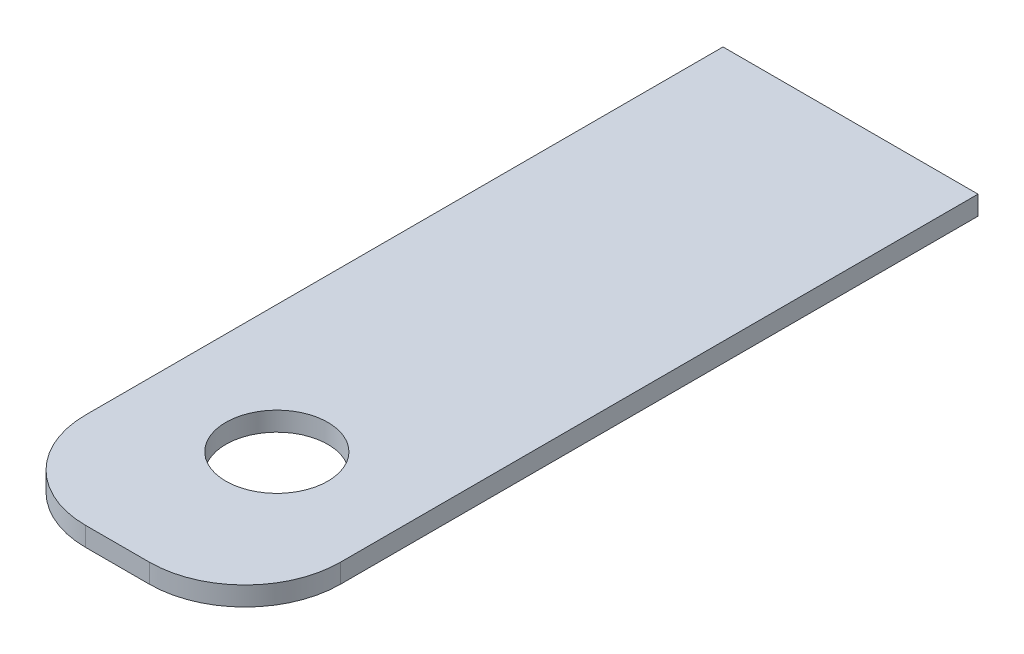
SolidWorks part; units mm, degrees
material "6061-T6 (SS)"
ref_plane "Front Plane" through (0, 0, 0) normal (0, 0, 1) x (1, 0, 0)
ref_plane "Top Plane" through (0, 0, 0) normal (0, 1, 0) x (1, 0, 0)
ref_plane "Right Plane" through (0, 0, 0) normal (1, 0, 0) x (0, 0, -1)
sketch "Sketch1" plane through (0, 0, 0) normal (0, 1, 0) x (1, 0, 0)
  line L1 (0, 0) -> (80, 0)
  line L2 (0, 0) -> (0, -230)
  line L3 (0, -230) -> (80, -230)
  line L4 (80, 0) -> (80, -230)
  dimension "D1" = 80
  dimension "D2" = 230
extrude "Boss-Extrude1" add sketch "Sketch1" along normal blind 6
sketch "Sketch5" plane through (0, 6, 0) normal (0, 1, 0) x (1, 0, 0)
  circle A0 centre (40, -180) radius 20 construction
  circle A1 centre (40, -180) radius 20
  point P1 (40, -180)
hole_wizard "Ø32.0 (32) Diameter Hole1" positions "Sketch5" profile "Sketch6" hole size "Ø32.0" standard "DIN" end condition through all
sketch "Sketch6" plane through (40, 6, 180) normal (1, 0, 0) x (0, 0, 1)
  line L0 (0, 0) -> (0, 6)
  line L1 (0, 6) -> (16, 6)
  line L2 (16, 6) -> (16, 0)
  line L5 (16, 0) -> (0, 0)
  line L11 (0, -6.35) -> (0, 107.95) construction
  dimension "Thru Hole Dia." = 32
  dimension "Thru Hole Depth" = 6
fillet "Fillet1" radius 30 2 edges at (0, 3, 230) (80, 3, 230)
